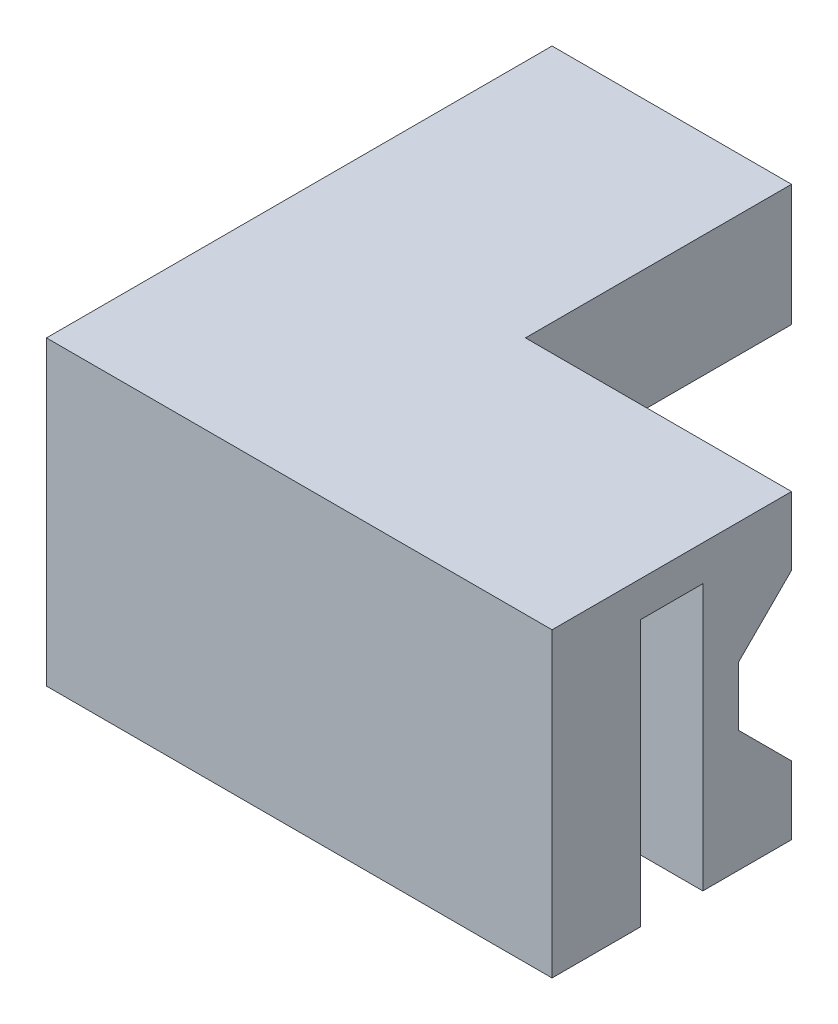
SolidWorks part; units mm, degrees
ref_plane "Front Plane" through (0, 0, 0) normal (0, 0, 1) x (1, 0, 0)
ref_plane "Top Plane" through (0, 0, 0) normal (0, 1, 0) x (1, 0, 0)
ref_plane "Right Plane" through (0, 0, 0) normal (1, 0, 0) x (0, 0, -1)
sketch "Sketch1" plane through (0, 0, 0) normal (0, 1, 0) x (1, 0, 0)
  line L0 (0, 0) -> (0, 3.5)
  line L1 (0, 3.5) -> (15, 3.5)
  line L2 (15, 3.5) -> (15, 18.5)
  line L3 (15, 18.5) -> (18.5, 18.5)
  line L4 (18.5, 18.5) -> (18.5, 0)
  line L5 (18.5, 0) -> (0, 0)
  line L6 (-5, 8.5) -> (10, 8.5)
  line L7 (10, 8.5) -> (10, 23.5)
  line L8 (10, 23.5) -> (23.5, 23.5)
  line L9 (23.5, 23.5) -> (23.5, -5)
  line L10 (23.5, -5) -> (-5, -5)
  line L11 (-5, -5) -> (-5, 8.5)
  dimension "D1" = 3.5
  dimension "D2" = 3.5
  dimension "D3" = 15
  dimension "D4" = 15
  dimension "D5" = 5
extrude "Boss-Extrude1" add sketch "Sketch1" along normal blind 15
sketch "Sketch2" plane through (0, 0, -8.5) normal (0, 0, -1) x (-1, 0, 0)
  line L0 (9.1398, 10.15) -> (-10, 10.15)
  line L1 (-10, 15) -> (5, 15) construction
  line L2 (9.1398, 6.85) -> (-10, 6.85)
  line L3 (-10, 10.15) -> (-10, 6.85)
  line L4 (-10, 15) -> (-10, 0) construction
  line L5 (9.1398, 10.15) -> (9.1398, 6.85)
  dimension "D1" = 4.85
  dimension "D2" = 3.3
extrude "Cut-Extrude1" cut sketch "Sketch2" against normal offset from surface (3 mm away) 2 up to face at (7.5, 7.5, -3.5)
chamfer "Chamfer1" distance 3 angle 45 2 edges at (2.5, 6.85, -8.5) (2.5, 10.15, -8.5)
sketch "Sketch4" plane through (0, 15, 0) normal (0, 1, 0) x (1, 0, 0)
  line L0 (-5, 8.5) -> (10, 8.5)
  line L1 (10, 8.5) -> (10, 23.5)
  line L2 (10, 23.5) -> (23.5, 23.5)
  line L3 (23.5, 23.5) -> (23.5, -5)
  line L4 (23.5, -5) -> (-5, -5)
  line L5 (-5, -5) -> (-5, 8.5)
extrude "Boss-Extrude2" add sketch "Sketch4" along normal blind 2
sketch "Sketch5" plane through (0, 0, 0) normal (0, -1, 0) x (1, 0, 0)
  line L0 (0, 0) -> (-5, 0)
  line L1 (-5, -8.5) -> (-5, 5) construction
  line L2 (-5, 0) -> (-5, -3.5)
  line L3 (-5, -3.5) -> (15, -3.5)
  line L4 (15, -3.5) -> (15, -24.3248)
  line L5 (15, -24.3248) -> (18.5, -24.3248)
  line L6 (18.5, -24.3248) -> (18.5, 0)
  line L7 (18.5, 0) -> (0, 0)
  line L8 (15, -3.5) -> (0, -3.5) construction
  line L9 (18.5, 0) -> (18.5, -18.5) construction
  line L10 (23.5, -23.5) -> (10, -23.5) construction
extrude "Cut-Extrude2" cut sketch "Sketch5" against normal up to surface (15 mm away) up to face at (11.1667, 15, -7.3333)
sketch "Sketch6" plane through (10, 0, 0) normal (-1, 0, 0) x (0, 0, 1)
  line L0 (-5.5, 10.15) -> (-5.5, 6.85)
  line L1 (-5.5, 6.85) -> (-8.5, 3.85)
  line L2 (-8.5, 3.85) -> (-8.5, 0)
  line L3 (-8.5, 0) -> (-23.5, 0)
  line L4 (-23.5, 0) -> (-23.5, 10.15)
  line L5 (-23.5, 17) -> (-23.5, 0) construction
  line L6 (-23.5, 10.15) -> (-5.5, 10.15)
extrude "Cut-Extrude3" cut sketch "Sketch6" against normal up to surface (8.5 mm away) up to face at (18.5, 7.5, -11.75)
ref_plane "Plane1" through (-15, 0, 0) normal (-1, 0, 0) x (0, 0, 1)
mirror "Mirror5" about plane through (-15, 0, 0) normal (-1, 0, 0) of bodies 105
sketch "Sketch7" plane through (0, 0, 0) normal (0, -1, 0) x (1, 0, 0)
  line L1 (-7.5726, -42.809) -> (37.5726, -42.809)
  line L2 (-7.5726, -42.809) -> (-7.5726, 35.809)
  line L3 (-7.5726, 35.809) -> (37.5726, 35.809)
  line L4 (37.5726, -42.809) -> (37.5726, 35.809)
  line L5 (-7.5726, -42.809) -> (37.5726, 35.809) construction
  line L6 (-7.5726, 35.809) -> (37.5726, -42.809) construction
  point P0 (15, -3.5)
extrude "Cut-Extrude4" cut sketch "Sketch7" against normal through all both and the other way through all
